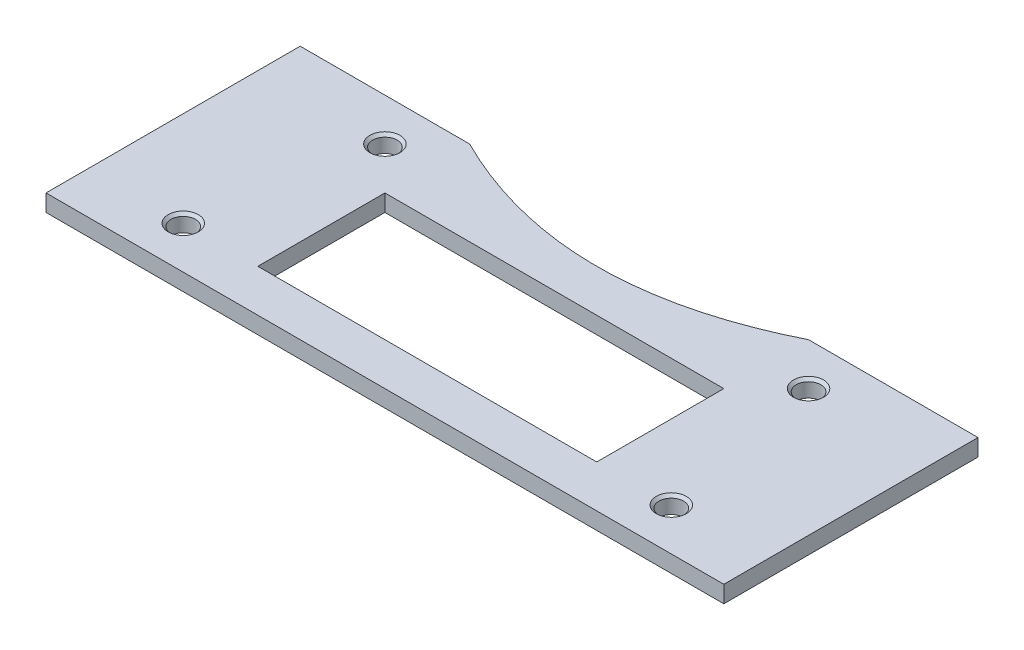
SolidWorks part; units mm, degrees
ref_plane "前视基准面" through (0, 0, 0) normal (0, 0, 1) x (1, 0, 0)
ref_plane "上视基准面" through (0, 0, 0) normal (0, 1, 0) x (1, 0, 0)
ref_plane "右视基准面" through (0, 0, 0) normal (1, 0, 0) x (0, 0, -1)
other "Configuration Table"
sketch "草图1" plane through (0, 0, 0) normal (0, 1, 0) x (1, 0, 0)
  line L0 (0, 0) -> (80, 0)
  line L2 (0, 0) -> (0, 30)
  line L3 (0, 30) -> (80, 30)
  line L4 (80, 0) -> (80, 30)
  dimension "D1" = 80
  dimension "D2" = 30
extrude "凸台-拉伸1" add sketch "草图1" along normal blind 2 contours L3 L4 L0 L2
sketch "草图2" plane through (0, 2, 0) normal (0, 1, 0) x (1, 0, 0)
  line L0 (11.2, 5) -> (68.8, 5) construction
  line L2 (40, 20) -> (10.7614, 20) construction
  line L3 (0, 0) -> (80, 0) construction
  line L4 (40, 20) -> (67.7357, 20) construction
  line L5 (0, 0) -> (0, 30) construction
  line L6 (20, 20) -> (60, 20)
  line L7 (20, 20) -> (20, 5)
  line L8 (0, 0) -> (0, 30) construction
  line L9 (0, 30) -> (80, 30) construction
  line L10 (80, 0) -> (80, 30) construction
  line L11 (20, 5) -> (60, 5)
  line L13 (60, 20) -> (60, 5)
  circle A0 centre (15, 25) radius 1
  circle A1 centre (65, 25) radius 1
  circle A2 centre (11.2, 5) radius 1
  circle A3 centre (68.8, 5) radius 1
  point P10 (15, 25)
  point P11 (65, 25)
  point P17 (11.2, 5)
  point P18 (68.8, 5)
  dimension "D2" = 5
  dimension "D4" = 15
  dimension "D1" = 2
  dimension "D10" = 2
  dimension "D11" = 2
  dimension "D3" = 2
  dimension "D5" = 5
  dimension "D6" = 15
  dimension "D7" = 5
  dimension "D8" = 11.2
  dimension "D9" = 5
  dimension "D12" = 11.2
  dimension "D13" = 50
  dimension "D14" = 57.6
  dimension "D15" = 20
  dimension "D16" = 15
  dimension "D17" = 5
  dimension "D18" = 20
sketch "草图4" plane through (0, 2, 0) normal (0, 1, 0) x (1, 0, 0)
  point P0 (15, 25)
  point P3 (11.2, 5)
  point P6 (65, 25)
  point P9 (68.8, 5)
hole_wizard "M3.5 螺纹孔1" positions "草图4" profile "草图5" tap size "M3.5" standard "GB" end condition through all
sketch "草图5" plane through (15, 2, -25) normal (1, 0, 0) x (0, 0, 1)
  line L0 (0, 0) -> (0, 2)
  line L1 (0, 2) -> (1.45, 2)
  line L2 (1.45, 2) -> (1.45, 0.325)
  line L3 (1.45, 0.325) -> (1.775, 0)
  line L5 (1.775, 0) -> (0, 0)
  line L6 (-1.45, 0.325) -> (-1.775, 0) construction
  line L11 (0, -6.35) -> (0, 107.95) construction
  dimension "通孔螺纹孔钻头直径" = 2.9
  dimension "通孔螺纹孔钻头深度" = 2
  dimension "近端锥形沉头孔直径" = 3.55
  dimension "近端锥形沉头孔角度" = 90
cosmetic thread "孔螺蚊线1" parameters "D2"=3.5
cosmetic thread "孔螺蚊线2" parameters "D2"=3.5
cosmetic thread "孔螺蚊线3" parameters "D2"=3.5
cosmetic thread "孔螺蚊线4" parameters "D2"=3.5
extrude "切除-拉伸2" cut sketch "草图2" against normal blind 10
sketch "草图7" plane through (0, 2, 0) normal (0, 1, 0) x (1, 0, 0)
  line L0 (20, 20) -> (20, 30) construction
  line L1 (0, 30) -> (80, 30) construction
  line L2 (60, 20) -> (60, 30) construction
  line L4 (60, 30) -> (20, 30)
  line L5 (40, 20) -> (40, 30) construction
  line L6 (60, 20) -> (20, 20) construction
  spline S1 degree 2 poles (20, 30) (40, 20) (60, 30) knots 0 0 0 1 1 1
extrude "切除-拉伸5" cut sketch "草图7" against normal blind 10
